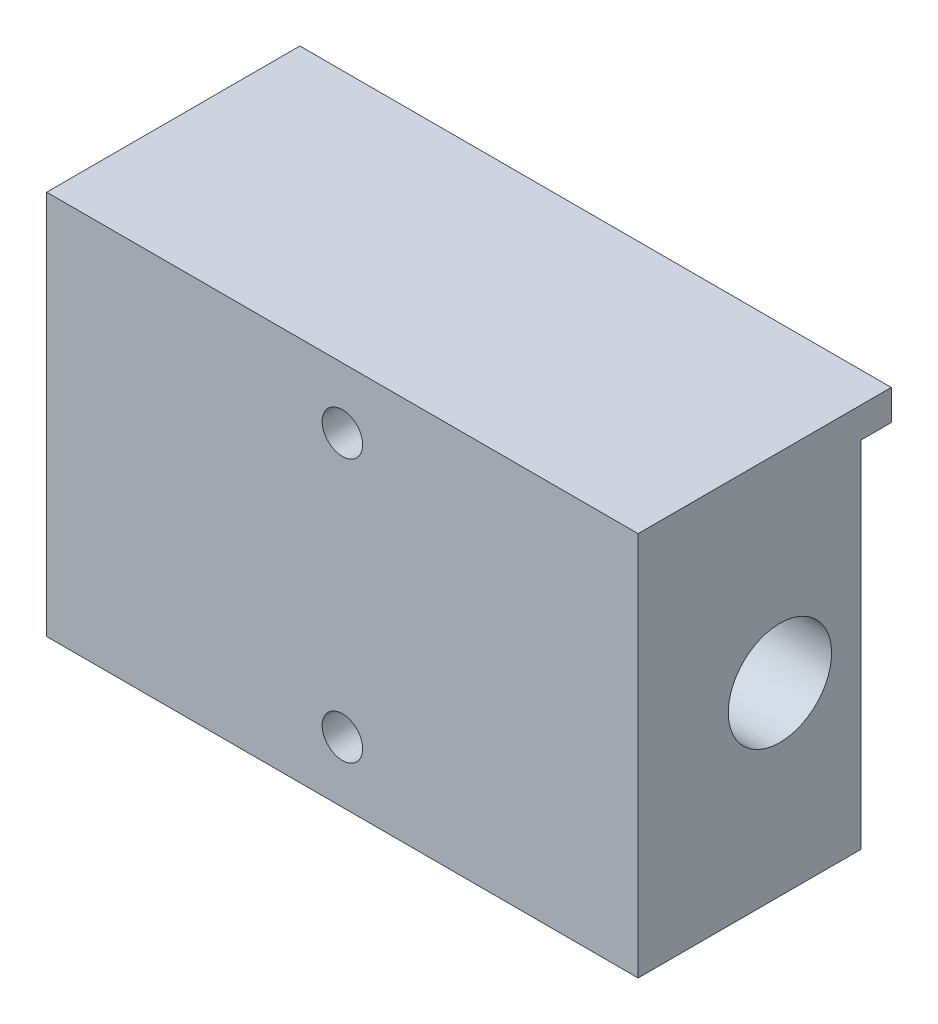
SolidWorks part; units mm, degrees
ref_plane "Alzado" through (0, 0, 0) normal (0, 0, 1) x (1, 0, 0)
ref_plane "Planta" through (0, 0, 0) normal (0, 1, 0) x (1, 0, 0)
ref_plane "Vista lateral" through (0, 0, 0) normal (1, 0, 0) x (0, 0, -1)
sketch "Croquis1" plane through (0, 0, 0) normal (0, 0, 1) x (1, 0, 0)
  line L1 (0, 0) -> (58.4, 0)
  line L2 (0, 0) -> (0, 38)
  line L3 (0, 38) -> (58.4, 38)
  line L4 (58.4, 0) -> (58.4, 38)
  dimension "D1" = 38
  dimension "D2" = 58.4
extrude "Saliente-Extruir1" add sketch "Croquis1" along normal blind 22
sketch "Croquis2" plane through (58.4, 0, 0) normal (1, 0, 0) x (0, 0, -1)
  circle A0 centre (-8, 18.2363) radius 5.1
  dimension "D1" = 10.2
  dimension "D2" = 8
extrude "Cortar-Extruir1" cut sketch "Croquis2" against normal through all
hole_wizard "Taladros de espiga de Ø4.0mm2" positions "Croquis4" profile "Croquis5" hole size "Ø4.0" standard "DIN"
sketch "Croquis4" plane through (0, 0, 22) normal (0, 0, 1) x (1, 0, 0)
  line L0 (0, 32) -> (58.4, 32) construction
  line L1 (0, 38) -> (0, 0) construction
  line L2 (58.4, 0) -> (58.4, 38) construction
  line L5 (58.4, 6) -> (0, 6) construction
  line L7 (58.4, 38) -> (0, 38) construction
  line L8 (29.2, 38) -> (29.2, 0) construction
  line L9 (0, 0) -> (58.4, 0) construction
  point P24 (29.2, 32)
  point P26 (29.2, 6)
  dimension "D1" = 6
  dimension "D2" = 6
sketch "Croquis5" plane through (29.2, 6, 22) normal (1, 0, 0) x (0, -1, 0)
  line L0 (0, 0) -> (0, 13.2017)
  line L1 (0, 13.2017) -> (2, 12)
  line L2 (2, 12) -> (2, 0)
  line L5 (2, 0) -> (0, 0)
  line L10 (0, 13.2017) -> (-2, 12) construction
  line L11 (0, -6.35) -> (0, 107.95) construction
  dimension "Diámetro de taladro" = 4
  dimension "Profundidad de taladro" = 12
  dimension "Ángulo de perforador" = 118
sketch "Croquis6" plane through (0, 0, 0) normal (0, 0, -1) x (-1, 0, 0)
  line L1 (-58.4, 35) -> (0, 35)
  line L2 (-58.4, 35) -> (-58.4, 38)
  line L3 (-58.4, 38) -> (0, 38)
  line L4 (0, 35) -> (0, 38)
  point P5 (0, 0)
  dimension "D1" = 3
extrude "Saliente-Extruir2" add sketch "Croquis6" along normal blind 3
